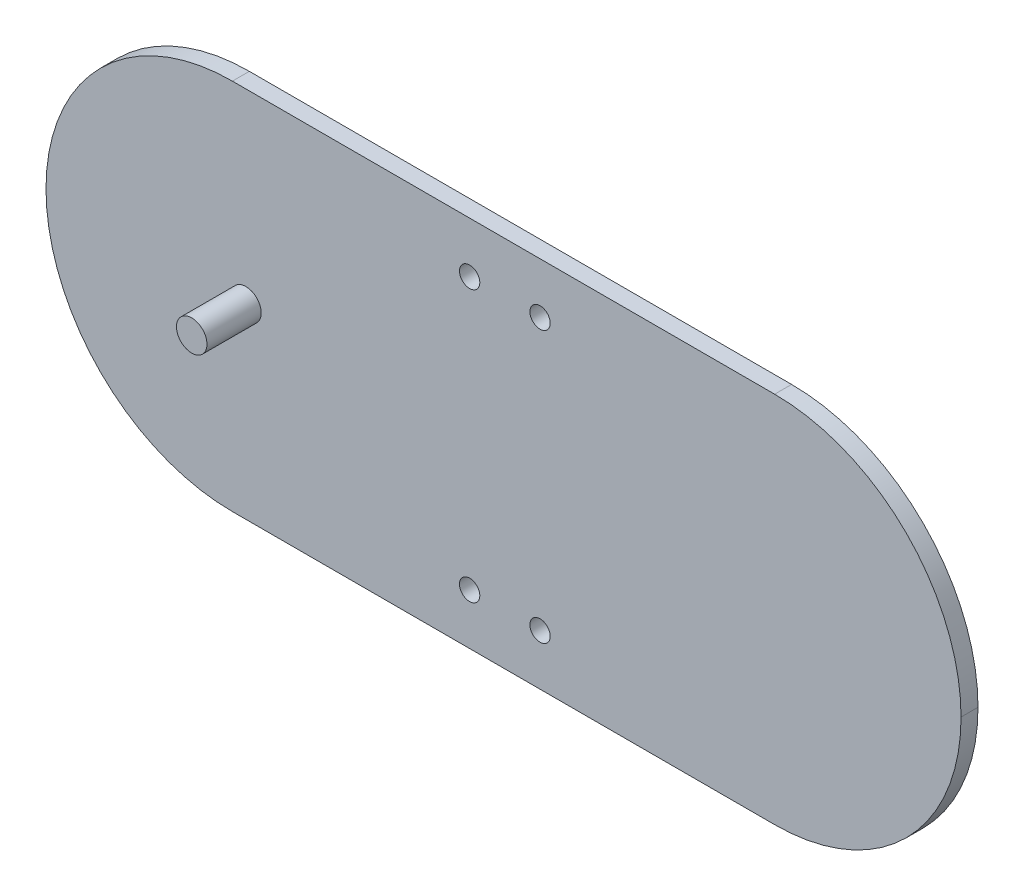
SolidWorks part; units mm, degrees
ref_plane "Front Plane" through (0, 0, 0) normal (0, 0, 1) x (1, 0, 0)
ref_plane "Top Plane" through (0, 0, 0) normal (0, 1, 0) x (1, 0, 0)
ref_plane "Right Plane" through (0, 0, 0) normal (1, 0, 0) x (0, 0, -1)
sketch "Sketch1" plane through (0, 0, 0) normal (0, 0, 1) x (1, 0, 0)
  line L1 (67.5, 27.5) -> (-67.5, 27.5)
  line L2 (67.5, 27.5) -> (67.5, -27.5)
  line L3 (67.5, -27.5) -> (-67.5, -27.5)
  line L4 (-67.5, 27.5) -> (-67.5, -27.5)
  line L5 (67.5, 27.5) -> (-67.5, -27.5) construction
  line L6 (67.5, -27.5) -> (-67.5, 27.5) construction
  point P0 (0, 0)
  dimension "D1" = 55
  dimension "D2" = 135
extrude "Boss-Extrude1" add sketch "Sketch1" along normal blind 2.5
fillet "Fillet1" radius 27.5 4 edges at (-67.5, -27.5, 1.25) (-67.5, 27.5, 1.25) (67.5, -27.5, 1.25) (67.5, 27.5, 1.25)
sketch "Sketch2" plane through (0, 0, 2.5) normal (0, 0, 1) x (1, 0, 0)
  line L0 (0, 0) -> (0, 20)
  line L1 (0, 20) -> (-5, 20)
  line L2 (-5, 20) -> (5.39, 20)
  circle A0 centre (-5, 20) radius 1.5
  circle A1 centre (5.39, 20) radius 1.5
  dimension "D4" = 3
  dimension "D5" = 3
  dimension "D1" = 20
  dimension "D2" = 5
  dimension "D3" = 10.39
extrude "Cut-Extrude1" cut sketch "Sketch2" against normal blind 2.5 contours A0 | A1 region at (-6.4576, 20, 2.5) region at (5.39, 21.4576, 2.5)
mirror "Mirror1" about plane through (0, 0, 0) normal (0, 1, 0) of "Cut-Extrude1"
sketch "Sketch4" plane through (0, 0, 2.5) normal (0, 0, 1) x (1, 0, 0)
  line L0 (0, 0) -> (-38, 0)
  circle A0 centre (-38, 0) radius 2.25
  dimension "D2" = 4.5
  dimension "D1" = 38
extrude "Boss-Extrude2" add sketch "Sketch4" along normal blind 8 contours A0 region at (-40.1864, 0, 2.5)
